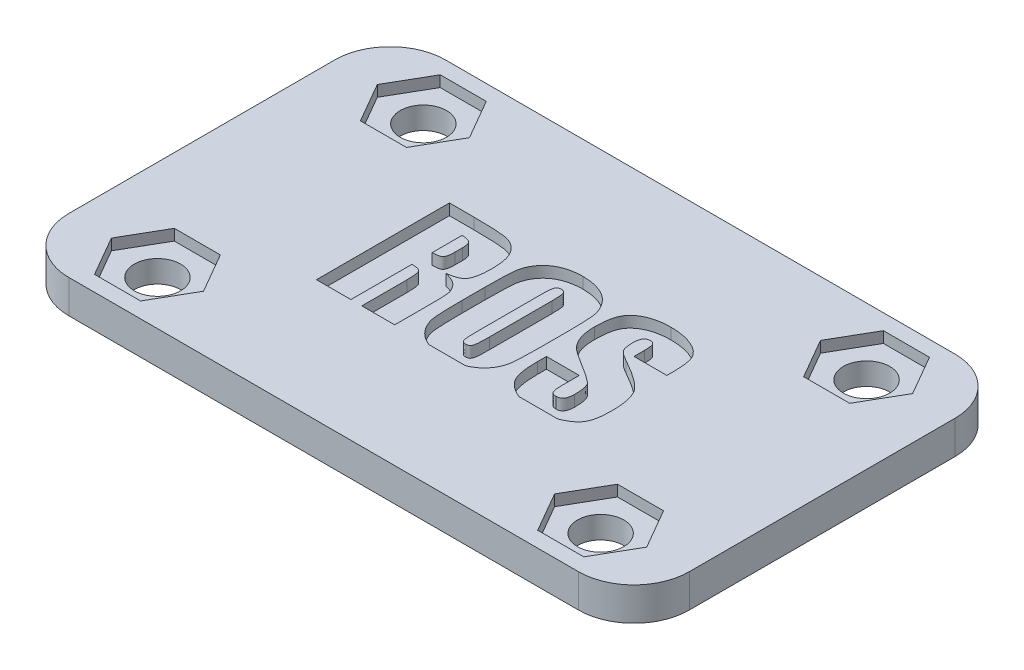
SolidWorks part; units mm, degrees
ref_plane "Front Plane" through (0, 0, 0) normal (0, 0, 1) x (1, 0, 0)
ref_plane "Top Plane" through (0, 0, 0) normal (0, 1, 0) x (1, 0, 0)
ref_plane "Right Plane" through (0, 0, 0) normal (1, 0, 0) x (0, 0, -1)
sketch "Sketch1" plane through (0, 0, 0) normal (0, 1, 0) x (1, 0, 0)
  line L1 (-28, 17) -> (28, 17)
  line L2 (-28, 17) -> (-28, -17)
  line L3 (-28, -17) -> (28, -17)
  line L4 (28, 17) -> (28, -17)
  line L5 (-28, 17) -> (28, -17) construction
  line L6 (-28, -17) -> (28, 17) construction
  point P0 (0, 0)
  dimension "D1" = 34
  dimension "D2" = 56
extrude "Boss-Extrude1" add sketch "Sketch1" along normal blind 3
sketch "Sketch2" plane through (0, 3, 0) normal (0, 1, 0) x (1, 0, 0)
  circle A0 centre (-20, 12) radius 2.09
  circle A1 centre (-20, -12) radius 2.09
  point P4 (0, 0)
  point P7 (0, 0)
  dimension "D1" = 4.18
  dimension "D2" = 24
  dimension "D3" = 12
  dimension "D4" = 20
extrude "Cut-Extrude1" cut sketch "Sketch2" against normal through all
mirror "Mirror1" about plane through (0, 0, 0) normal (1, 0, 0) of "Cut-Extrude1"
fillet "Fillet1" radius 5 4 edges at (28, 1.5, -17) (28, 1.5, 17) (-28, 1.5, 17) (-28, 1.5, -17)
sketch "Sketch3" plane through (0, 3, 0) normal (0, 1, 0) x (1, 0, 0)
  line L1 (-15.8431, 12) -> (-17.9215, 15.6)
  line L2 (-17.9215, 15.6) -> (-22.0785, 15.6)
  line L3 (-22.0785, 15.6) -> (-24.1569, 12)
  line L4 (-24.1569, 12) -> (-22.0785, 8.4)
  line L5 (-22.0785, 8.4) -> (-17.9215, 8.4)
  line L6 (-17.9215, 8.4) -> (-15.8431, 12)
  line L7 (24.1569, 12) -> (22.0785, 15.6)
  line L8 (22.0785, 15.6) -> (17.9215, 15.6)
  line L9 (17.9215, 15.6) -> (15.8431, 12)
  line L10 (15.8431, 12) -> (17.9215, 8.4)
  line L11 (17.9215, 8.4) -> (22.0785, 8.4)
  line L12 (22.0785, 8.4) -> (24.1569, 12)
  line L13 (-23, -17) -> (23, -17) construction
  circle A0 centre (-20, 12) radius 3.6 construction
  circle A1 centre (20, 12) radius 3.6 construction
  circle A2 centre (-20, 12) radius 2.09 construction
  circle A3 centre (20, 12) radius 2.09 construction
  dimension "D1" = 7.2
extrude "Cut-Extrude2" cut sketch "Sketch3" against normal blind 1
mirror "Mirror2" about plane through (0, 0, 0) normal (0, 0, 1) of "Cut-Extrude2"
sketch "Sketch4" plane through (0, 3, 0) normal (0, 1, 0) x (1, 0, 0)
  line L0 (-17, -6) -> (17, -6)
  line L1 (-11.6471, 6) -> (-9.4103, 6)
  line L2 (-4.5882, -2.7949) -> (-4.5882, -6)
  line L3 (-4.5882, -6) -> (-7.5529, -6)
  line L4 (-7.5529, -6) -> (-7.5529, -1.9412)
  line L5 (-8.5412, -0.4941) -> (-8.5412, -6)
  line L6 (-8.5412, -6) -> (-11.6471, -6)
  line L7 (-11.6471, -6) -> (-11.6471, 6)
  line L8 (-8.5412, 4.0235) -> (-8.5412, 1.3412)
  line L9 (-7.5529, 2.4287) -> (-7.5529, 3.0926)
  line L10 (-3.4588, -1.0324) -> (-3.4588, 1.0324)
  line L11 (3.7412, 1.0324) -> (3.7412, -1.0324)
  line L12 (-0.3529, 2.9757) -> (-0.3529, -2.7397)
  line L13 (0.6353, -2.6493) -> (0.6353, 2.9757)
  line L14 (11.6471, 2.3294) -> (8.6824, 2.3294)
  line L15 (8.6824, 2.3294) -> (8.6824, 3.2779)
  line L16 (4.7294, -2.4287) -> (4.7294, -1.6235)
  line L17 (4.7294, -1.6235) -> (7.6941, -1.6235)
  line L18 (7.6941, -1.6235) -> (7.6941, -3.1787)
  line L19 (11.6471, 2.8125) -> (11.6471, 2.3294)
  spline S0 degree 3 poles (-9.4103, 6) (-9.0669, 6.0012) (-8.5749, 5.9955) (-7.9492, 5.9771) (-7.5475, 5.9606) (-7.1909, 5.9363) (-6.8797, 5.9081) (-6.6138, 5.8763) (-6.3865, 5.8368) (-6.1862, 5.7853) (-6.0014, 5.7178) (-5.8245, 5.6374) (-5.6576, 5.5369) (-5.502, 5.419) (-5.352, 5.2894) (-5.2155, 5.1388) (-5.0841, 4.9743) (-4.9654, 4.7866) (-4.865, 4.5736) (-4.7788, 4.3358) (-4.7089, 4.0722) (-4.6548, 3.7831) (-4.5993, 3.3474) (-4.5915, 3.0059) (-4.5882, 2.7706) knots 0 0 0 0 0.148881 0.213303 0.271377 0.323138 0.368276 0.406827 0.439217 0.468212 0.496346 0.524443 0.552325 0.580569 0.609028 0.638128 0.668547 0.700209 0.734143 0.770448 0.80973 0.852244 0.897872 1 1 1 1
  spline S1 degree 3 poles (-4.5882, 2.7706) (-4.5847, 2.5592) (-4.5991, 2.256) (-4.6321, 1.8709) (-4.6732, 1.6245) (-4.7199, 1.4058) (-4.7787, 1.2138) (-4.8506, 1.0509) (-4.9341, 0.9125) (-5.0352, 0.7962) (-5.1554, 0.6939) (-5.2985, 0.6065) (-5.4611, 0.5289) (-5.6443, 0.4631) (-5.9295, 0.3905) (-6.1567, 0.3569) (-6.3154, 0.3441) knots 0 0 0 0 0.18379 0.264137 0.336087 0.400976 0.458649 0.510492 0.555595 0.598692 0.64408 0.692369 0.744168 0.800637 0.861472 1 1 1 1
  spline S2 degree 3 poles (-6.3154, 0.3441) (-6.1721, 0.3049) (-5.9643, 0.2494) (-5.706, 0.1522) (-5.5411, 0.0744) (-5.3931, -0.0045) (-5.2653, -0.0902) (-5.1556, -0.181) (-5.0387, -0.3053) (-4.9212, -0.4619) (-4.8041, -0.6448) (-4.7194, -0.8218) (-4.6697, -0.9719) (-4.6478, -1.1078) (-4.6293, -1.2429) (-4.6181, -1.4146) (-4.6068, -1.622) (-4.5986, -1.8647) (-4.5883, -2.2595) (-4.5915, -2.5736) (-4.5882, -2.7949) knots 0 0 0 0 0.11023 0.159227 0.204341 0.24532 0.283418 0.318243 0.350629 0.40972 0.463107 0.511383 0.554826 0.57974 0.613275 0.655917 0.707227 0.767226 0.835926 1 1 1 1
  spline S3 degree 3 poles (-7.5529, -1.9412) (-7.5542, -1.7934) (-7.554, -1.5834) (-7.5737, -1.3189) (-7.5901, -1.1553) (-7.6124, -1.0148) (-7.6369, -0.8974) (-7.67, -0.8034) (-7.7079, -0.7287) (-7.7573, -0.6684) (-7.8245, -0.6234) (-7.9036, -0.5807) (-8.0005, -0.548) (-8.1132, -0.5251) (-8.2947, -0.5004) (-8.4396, -0.4949) (-8.5412, -0.4941) knots 0 0 0 0 0.208712 0.296135 0.374434 0.440653 0.497065 0.543362 0.580978 0.614872 0.652041 0.694298 0.741574 0.795735 0.856514 1 1 1 1
  spline S4 degree 3 poles (-8.5412, 1.3412) (-8.3851, 1.3403) (-8.1682, 1.3525) (-7.9124, 1.4151) (-7.791, 1.4674) (-7.718, 1.5343) (-7.6711, 1.6021) (-7.6355, 1.6922) (-7.6049, 1.8009) (-7.5815, 1.9295) (-7.5561, 2.1403) (-7.5563, 2.3097) (-7.5529, 2.4287) knots 0 0 0 0 0.26319 0.361521 0.442778 0.481273 0.526535 0.580255 0.643242 0.716208 0.799609 1 1 1 1
  spline S5 degree 3 poles (-7.5529, 3.0926) (-7.5545, 3.251) (-7.5655, 3.4729) (-7.66, 3.7254) (-7.7586, 3.8532) (-7.9007, 3.9314) (-8.1584, 4.0148) (-8.3828, 4.0205) (-8.5412, 4.0235) knots 0 0 0 0 0.296724 0.405999 0.497474 0.590179 0.702697 1 1 1 1
  spline S6 degree 3 poles (3.7412, -1.0324) (3.7385, -1.3125) (3.74, -1.7169) (3.7317, -2.2339) (3.7191, -2.5721) (3.71, -2.8766) (3.6939, -3.1487) (3.6767, -3.3877) (3.6517, -3.661) (3.6003, -3.9749) (3.4883, -4.3317) (3.3296, -4.6711) (3.1303, -4.9928) (2.887, -5.2876) (2.6016, -5.5477) (2.2768, -5.7719) (1.913, -5.9572) (1.5147, -6.1011) (0.926, -6.2488) (0.4589, -6.2785) (0.1412, -6.2824) knots 0 0 0 0 0.112809 0.162854 0.208179 0.249065 0.285542 0.317902 0.345566 0.396043 0.445676 0.495616 0.546553 0.597656 0.649001 0.701564 0.75612 0.812885 0.871769 1 1 1 1
  spline S7 degree 3 poles (0.1412, -6.2824) (-0.1648, -6.2831) (-0.6144, -6.2452) (-1.1897, -6.1149) (-1.5848, -5.9757) (-1.9508, -5.7992) (-2.2779, -5.5765) (-2.5736, -5.321) (-2.8223, -5.0216) (-3.0318, -4.6996) (-3.1943, -4.3589) (-3.3103, -4.0053) (-3.368, -3.6952) (-3.392, -3.4245) (-3.4096, -3.1854) (-3.4246, -2.9111) (-3.4383, -2.603) (-3.4461, -2.2596) (-3.4555, -1.7324) (-3.458, -1.3191) (-3.4588, -1.0324) knots 0 0 0 0 0.123179 0.180929 0.237119 0.291548 0.344027 0.396062 0.448383 0.50021 0.550408 0.599943 0.649656 0.677029 0.709392 0.746168 0.787661 0.833574 0.884513 1 1 1 1
  spline S8 degree 3 poles (-3.4588, 1.0324) (-3.4561, 1.3132) (-3.4578, 1.7177) (-3.4492, 2.2346) (-3.437, 2.5721) (-3.4266, 2.8773) (-3.4146, 3.1495) (-3.3962, 3.3884) (-3.3721, 3.6612) (-3.3171, 3.9747) (-3.206, 4.3317) (-3.0479, 4.6709) (-2.8464, 4.9909) (-2.6056, 5.2885) (-2.3171, 5.546) (-1.9944, 5.773) (-1.63, 5.9562) (-1.2327, 6.1053) (-0.6417, 6.2443) (-0.1769, 6.2856) (0.1412, 6.2824) knots 0 0 0 0 0.1131 0.162847 0.20817 0.249054 0.28581 0.317873 0.345536 0.396062 0.445693 0.495631 0.546315 0.597643 0.649205 0.701523 0.756077 0.812942 0.872041 1 1 1 1
  spline S9 degree 3 poles (0.1412, 6.2824) (0.4469, 6.2818) (0.8967, 6.2477) (1.4702, 6.1117) (1.8645, 5.9733) (2.2316, 5.7988) (2.5599, 5.5778) (2.8536, 5.3201) (3.1028, 5.0218) (3.3114, 4.6989) (3.4772, 4.3595) (3.5927, 4.0046) (3.6506, 3.6938) (3.6735, 3.4229) (3.6959, 3.1849) (3.7057, 2.911) (3.7213, 2.6031) (3.7275, 2.2595) (3.7434, 1.7325) (3.7366, 1.3191) (3.7412, 1.0324) knots 0 0 0 0 0.123202 0.180743 0.236944 0.291253 0.343988 0.395811 0.448142 0.499979 0.550314 0.59986 0.649873 0.677251 0.709348 0.746116 0.787617 0.833538 0.884493 1 1 1 1
  spline S10 degree 3 poles (0.6353, 2.9757) (0.6349, 3.1052) (0.6314, 3.2898) (0.6236, 3.523) (0.6121, 3.6693) (0.5991, 3.7965) (0.585, 3.9051) (0.5651, 3.9935) (0.5377, 4.0836) (0.4873, 4.1724) (0.3682, 4.2858) (0.2378, 4.3035) (0.1566, 4.3059) knots 0 0 0 0 0.245382 0.350014 0.44228 0.523563 0.592561 0.649714 0.69512 0.770679 0.840726 1 1 1 1
  spline S11 degree 3 poles (0.1566, 4.3059) (0.0809, 4.3097) (-0.0301, 4.2831) (-0.155, 4.2004) (-0.2173, 4.1263) (-0.2587, 4.0467) (-0.283, 3.962) (-0.3051, 3.8552) (-0.3211, 3.7245) (-0.3378, 3.5709) (-0.3473, 3.3184) (-0.3544, 3.1178) (-0.3529, 2.9757) knots 0 0 0 0 0.141273 0.207934 0.278501 0.320511 0.375555 0.443281 0.525523 0.622695 0.733336 1 1 1 1
  spline S12 degree 3 poles (-0.3529, -2.7397) (-0.3502, -2.9007) (-0.3519, -3.1295) (-0.3437, -3.4171) (-0.331, -3.5941) (-0.3222, -3.7459) (-0.3063, -3.8724) (-0.2896, -3.9735) (-0.2657, -4.0719) (-0.2162, -4.1673) (-0.0898, -4.2859) (0.0478, -4.3054) (0.1346, -4.3059) knots 0 0 0 0 0.263966 0.37491 0.47152 0.554902 0.624119 0.680394 0.722784 0.789642 0.853612 1 1 1 1
  spline S13 degree 3 poles (0.1346, -4.3059) (0.2255, -4.3075) (0.3671, -4.2777) (0.4949, -4.1446) (0.5422, -4.0365) (0.5704, -3.9275) (0.586, -3.8179) (0.6017, -3.6841) (0.615, -3.5252) (0.6226, -3.3412) (0.6323, -3.0464) (0.6344, -2.8132) (0.6353, -2.6493) knots 0 0 0 0 0.145036 0.209347 0.281953 0.327187 0.385478 0.455017 0.538188 0.634996 0.743262 1 1 1 1
  spline S14 degree 3 poles (8.6824, 3.2779) (8.6818, 3.4588) (8.6776, 3.7029) (8.6263, 3.9859) (8.5738, 4.1183) (8.4978, 4.207) (8.3666, 4.2877) (8.2475, 4.3082) (8.1662, 4.3059) knots 0 0 0 0 0.412843 0.553103 0.65361 0.73318 0.814494 1 1 1 1
  spline S15 degree 3 poles (8.1662, 4.3059) (8.076, 4.3052) (7.9379, 4.2803) (7.7902, 4.1738) (7.6998, 4.0667) (7.6311, 3.9284) (7.5692, 3.6856) (7.549, 3.4865) (7.5529, 3.3441) knots 0 0 0 0 0.212113 0.312859 0.418563 0.535756 0.66915 1 1 1 1
  spline S16 degree 3 poles (7.5529, 3.3441) (7.5516, 3.1611) (7.5694, 2.8413) (7.6434, 2.5283) (7.7029, 2.4044) knots 0 0 0 0 0.572651 1 1 1 1
  spline S17 degree 3 poles (7.7029, 2.4044) (7.7322, 2.3452) (7.7942, 2.2581) (7.8995, 2.147) (8.0059, 2.059) (8.1288, 1.9644) (8.3296, 1.8295) (8.496, 1.7357) (8.6118, 1.6699) knots 0 0 0 0 0.166753 0.269572 0.387216 0.516182 0.662459 1 1 1 1
  spline S18 degree 3 poles (8.6118, 1.6699) (8.9472, 1.484) (9.4257, 1.211) (10.0156, 0.8328) (10.3851, 0.5738) (10.7061, 0.3313) (11.0411, 0.0406) (11.2578, -0.1815) (11.3669, -0.3397) knots 0 0 0 0 0.335278 0.4813 0.612364 0.729739 0.832713 1 1 1 1
  spline S19 degree 3 poles (11.3669, -0.3397) (11.4674, -0.4836) (11.5941, -0.7269) (11.7151, -1.0863) (11.7938, -1.3946) (11.8552, -1.7344) (11.9148, -2.2468) (11.9294, -2.6482) (11.9294, -2.925) knots 0 0 0 0 0.195997 0.304678 0.423526 0.551406 0.690506 1 1 1 1
  spline S20 degree 3 poles (11.9294, -2.925) (11.9306, -3.1274) (11.921, -3.4206) (11.8877, -3.7962) (11.8559, -4.046) (11.8113, -4.2742) (11.7592, -4.4814) (11.6979, -4.6686) (11.6247, -4.8366) (11.5365, -4.9904) (11.4313, -5.1345) (11.31, -5.2737) (11.1701, -5.4062) (11.0125, -5.5328) (10.8359, -5.6506) (10.6422, -5.7639) (10.3591, -5.9089) (9.9729, -6.059) (9.2933, -6.2392) (8.7537, -6.28) (8.3868, -6.2824) knots 0 0 0 0 0.107307 0.155459 0.199907 0.240819 0.278648 0.313174 0.345124 0.37569 0.406967 0.439576 0.4735 0.509002 0.546638 0.58596 0.627987 0.715167 0.805112 1 1 1 1
  spline S21 degree 3 poles (8.3868, -6.2824) (8.1804, -6.2854) (7.8765, -6.2668) (7.481, -6.2177) (7.2012, -6.1639) (6.9326, -6.0967) (6.6761, -6.0115) (6.43, -5.9163) (6.1998, -5.8006) (5.9838, -5.6755) (5.7857, -5.5421) (5.6073, -5.3994) (5.4478, -5.2498) (5.3077, -5.0905) (5.1891, -4.9216) (5.0852, -4.7476) (5.0057, -4.5597) (4.9402, -4.3592) (4.8815, -4.1416) (4.8378, -3.9036) (4.7968, -3.6464) (4.767, -3.3696) (4.7367, -2.9616) (4.7296, -2.6457) (4.7294, -2.4287) knots 0 0 0 0 0.100145 0.147666 0.193464 0.238409 0.281993 0.324627 0.366464 0.406944 0.445764 0.482345 0.517706 0.551866 0.585155 0.617796 0.650099 0.683973 0.720175 0.759459 0.801374 0.84664 0.894618 1 1 1 1
  spline S22 degree 3 poles (7.6941, -3.1787) (7.6926, -3.2877) (7.7, -3.4427) (7.7093, -3.6394) (7.7266, -3.7627) (7.7414, -3.871) (7.7672, -3.9619) (7.7922, -4.038) (7.8328, -4.1177) (7.9024, -4.1962) (8.0568, -4.2904) (8.2004, -4.3038) (8.2963, -4.3059) knots 0 0 0 0 0.221449 0.31586 0.400263 0.474516 0.538003 0.591926 0.637412 0.719013 0.801608 1 1 1 1
  spline S23 degree 3 poles (8.2963, -4.3059) (8.3981, -4.3086) (8.5473, -4.2778) (8.713, -4.1688) (8.8065, -4.053) (8.8803, -3.9083) (8.9485, -3.6569) (8.9647, -3.4501) (8.9647, -3.3044) knots 0 0 0 0 0.223296 0.324627 0.430189 0.546596 0.679609 1 1 1 1
  spline S24 degree 3 poles (8.9647, -3.3044) (8.9649, -3.1381) (8.9574, -2.9001) (8.9286, -2.5983) (8.8949, -2.4078) (8.857, -2.2394) (8.7927, -2.0592) (8.7313, -1.9386) (8.6757, -1.875) knots 0 0 0 0 0.336674 0.481824 0.613234 0.728042 0.830673 1 1 1 1
  spline S25 degree 3 poles (8.6757, -1.875) (8.6126, -1.8041) (8.4954, -1.699) (8.3122, -1.5594) (8.137, -1.4289) (7.9303, -1.2881) (7.5985, -1.0708) (7.3298, -0.9089) (7.1426, -0.7941) knots 0 0 0 0 0.151175 0.250667 0.367276 0.49971 0.649705 1 1 1 1
  spline S26 degree 3 poles (7.1426, -0.7941) (6.9527, -0.6788) (6.6813, -0.5122) (6.34, -0.2922) (6.1235, -0.1475) (5.9316, -0.0168) (5.767, 0.1018) (5.6269, 0.2072) (5.4751, 0.3341) (5.311, 0.5032) (5.1361, 0.7318) (4.9799, 0.9943) (4.8394, 1.2899) (4.7229, 1.6247) (4.6172, 2.1551) (4.5843, 2.5772) (4.5882, 2.8721) knots 0 0 0 0 0.139497 0.199929 0.25485 0.30299 0.345648 0.382207 0.412998 0.469794 0.529711 0.593278 0.661207 0.734924 0.815133 1 1 1 1
  spline S27 degree 3 poles (4.5882, 2.8721) (4.5915, 3.089) (4.5956, 3.4033) (4.6361, 3.8052) (4.6748, 4.0719) (4.7257, 4.3157) (4.7856, 4.5371) (4.8612, 4.7336) (4.9459, 4.9098) (5.0448, 5.0692) (5.1582, 5.2159) (5.2818, 5.3578) (5.4237, 5.4859) (5.5773, 5.6088) (5.7441, 5.7233) (5.9262, 5.8266) (6.1895, 5.9555) (6.5504, 6.088) (7.1983, 6.2468) (7.715, 6.2821) (8.0691, 6.2824) knots 0 0 0 0 0.115094 0.16642 0.214115 0.25793 0.298418 0.335563 0.369391 0.401957 0.434786 0.46765 0.501588 0.535991 0.571894 0.608743 0.64693 0.727243 0.81197 1 1 1 1
  spline S28 degree 3 poles (8.0691, 6.2824) (8.2698, 6.2794) (8.5663, 6.2747) (8.9506, 6.2262) (9.223, 6.1872) (9.4831, 6.128) (9.7326, 6.0611) (9.9699, 5.979) (10.194, 5.8841) (10.4035, 5.7811) (10.5978, 5.6745) (10.7692, 5.555) (10.9282, 5.4368) (11.0618, 5.3035) (11.1838, 5.1702) (11.2823, 5.0262) (11.3651, 4.8734) (11.4309, 4.703) (11.491, 4.5119) (11.5377, 4.2929) (11.5805, 4.0489) (11.6097, 3.7769) (11.6403, 3.3624) (11.6468, 3.0376) (11.6471, 2.8125) knots 0 0 0 0 0.103081 0.151694 0.198641 0.244219 0.288419 0.331125 0.37288 0.413199 0.450863 0.486435 0.520313 0.552325 0.583055 0.612876 0.641566 0.672036 0.706398 0.744284 0.786764 0.83346 0.884523 1 1 1 1
  point P2 (0, -6)
  dimension "D1" = 34
  dimension "D2" = 6
extrude "Cut-Extrude3" cut sketch "Sketch4" against normal blind 1 contours S3 L4 L0 L2 S2 S1 S0 L1 L7 L5 S5 L9 S4 L8 | S9 S8 L10 S7 L0 S6 L11 S13 S12 L12 S11 S10 L13 | S28 S27 S26 S25 S24 S23 S22 L18 L17 L16 S21 L0 S20 S19 S18 S17 S16 S15 S14 L15 L14 L19 region at (-8.2424, 3, -0.0304) region at (8.2206, 3, -0.0264) region at (-3.1849, 3, 3.882)
